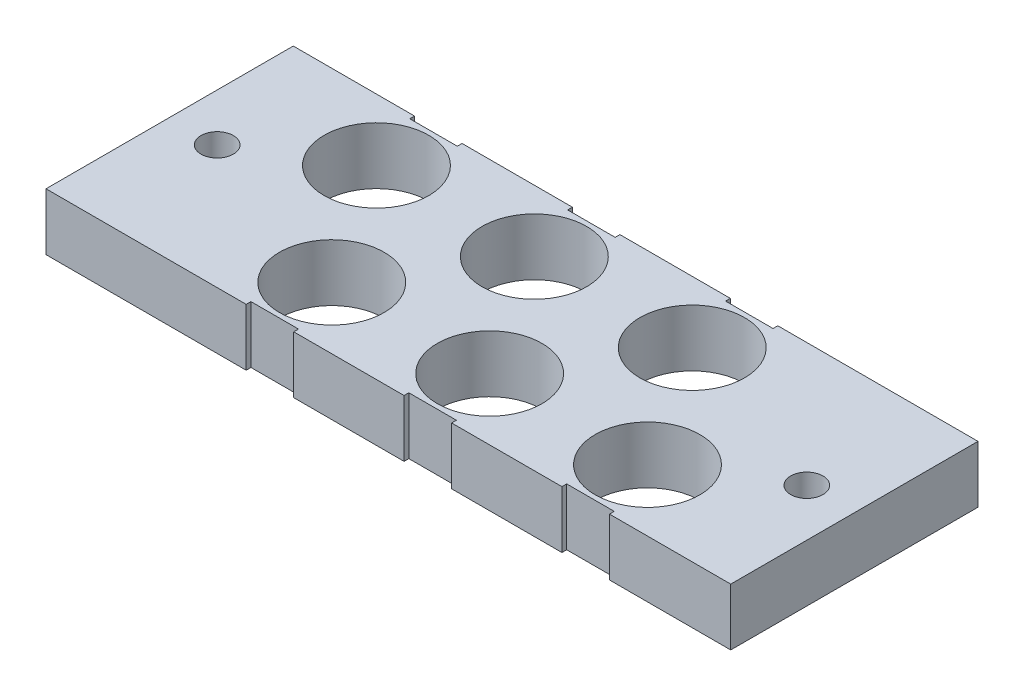
SolidWorks part; units mm, degrees
ref_plane "Front Plane" through (0, 0, 0) normal (0, 0, 1) x (1, 0, 0)
ref_plane "Top Plane" through (0, 0, 0) normal (0, 1, 0) x (1, 0, 0)
ref_plane "Right Plane" through (0, 0, 0) normal (1, 0, 0) x (0, 0, -1)
sketch "Sketch1" plane through (0, 0, 0) normal (0, 1, 0) x (1, 0, 0)
  line L0 (5.3864, -4.1649) -> (1.7864, -4.1649)
  line L1 (18.3864, -4.1649) -> (21.9864, -4.1649)
  line L2 (30.2864, -30.1649) -> (26.6864, -30.1649)
  line L3 (13.6864, -30.1649) -> (10.0864, -30.1649)
  line L4 (43.2864, -30.1649) -> (52.0364, -30.1649)
  line L5 (52.0364, -30.1649) -> (52.0364, -4.1649)
  line L6 (52.0364, -4.1649) -> (34.9864, -4.1649)
  line L7 (-11.2136, -4.1649) -> (-19.9636, -4.1649)
  line L8 (-19.9636, -4.1649) -> (-19.9636, -30.1649)
  line L9 (-19.9636, -30.1649) -> (-2.9136, -30.1649)
  line L10 (-14.9636, -4.1649) -> (-14.9636, -30.1649) construction
  line L11 (47.0364, -4.1649) -> (47.0364, -30.1649) construction
  circle A0 centre (-14.9636, -17.1649) radius 1.7
  circle A1 centre (47.0364, -17.1649) radius 1.7
  line B0 (34.9864, -17.1649) -> (34.9864, -4.1649)
  line B1 (10.0864, -30.1649) -> (6.0864, -30.1649)
  line B2 (-2.4136, -29.6649) -> (9.5864, -29.6649)
  line B3 (10.0864, -30.1649) -> (10.0864, -17.1649)
  line B4 (26.6864, -30.1649) -> (26.6864, -17.1649)
  line B5 (43.2864, -30.1649) -> (43.2864, -17.1649)
  line B6 (-2.9136, -17.1649) -> (-2.9136, -30.1649)
  line B7 (9.5864, -29.6649) -> (9.5864, -17.6649)
  line B8 (30.2864, -17.1649) -> (30.2864, -30.1649)
  line B9 (21.9864, -4.1649) -> (21.9864, -17.1649)
  line B10 (34.4864, -16.6649) -> (34.4864, -4.6649)
  line B11 (17.8864, -16.6649) -> (17.8864, -4.6649)
  line B12 (1.7864, -17.1649) -> (1.7864, -4.1649)
  line B13 (42.7864, -29.6649) -> (42.7864, -17.6649)
  line B14 (14.1864, -29.6649) -> (26.1864, -29.6649)
  line B15 (30.7864, -17.6649) -> (30.7864, -29.6649)
  line B16 (30.7864, -17.6649) -> (42.7864, -29.6649) construction
  line B17 (14.1864, -17.6649) -> (26.1864, -29.6649) construction
  line B18 (-2.4136, -17.6649) -> (9.5864, -29.6649) construction
  line B19 (43.2864, -17.1649) -> (30.2864, -17.1649)
  line B20 (1.2864, -16.6649) -> (1.2864, -4.6649)
  line B21 (14.1864, -17.6649) -> (14.1864, -29.6649)
  line B22 (26.6864, -30.1649) -> (22.6864, -30.1649)
  line B23 (30.2864, -30.1649) -> (34.2864, -30.1649)
  line B24 (43.2864, -30.1649) -> (39.2864, -30.1649)
  line B25 (-10.7136, -10.6649) -> (1.2864, -10.6649) construction
  line B26 (5.8864, -10.6649) -> (17.8864, -10.6649) construction
  line B27 (22.4864, -10.6649) -> (34.4864, -10.6649) construction
  line B28 (-2.4136, -23.6649) -> (9.5864, -23.6649) construction
  line B29 (14.1864, -23.6649) -> (26.1864, -23.6649) construction
  line B30 (30.7864, -23.6649) -> (42.7864, -23.6649) construction
  line B31 (-27.9152, -23.6649) -> (50.7342, -23.6649) construction
  line B32 (21.9864, -17.1649) -> (34.9864, -17.1649)
  line B33 (-27.9152, -10.6649) -> (50.7342, -10.6649) construction
  line B34 (28.4864, -16.6649) -> (28.4864, -4.6649) construction
  line B35 (36.7864, -17.6649) -> (36.7864, -29.6649) construction
  line B36 (20.1864, -17.6649) -> (20.1864, -29.6649) construction
  line B37 (11.8864, -16.6649) -> (11.8864, -4.6649) construction
  line B38 (3.5864, -17.6649) -> (3.5864, -29.6649) construction
  line B39 (-4.7136, -16.6649) -> (-4.7136, -4.6649) construction
  line B40 (22.4864, -4.6649) -> (22.4864, -16.6649)
  line B41 (22.4864, -16.6649) -> (34.4864, -16.6649)
  line B42 (34.4864, -4.6649) -> (22.4864, -4.6649)
  line B43 (34.4864, -16.6649) -> (22.4864, -4.6649) construction
  line B44 (34.4864, -4.6649) -> (22.4864, -16.6649) construction
  line B45 (34.9864, -4.1649) -> (30.9864, -4.1649)
  line B46 (21.9864, -4.1649) -> (25.9864, -4.1649)
  line B47 (30.9864, -4.1649) -> (30.9864, -4.6649)
  line B48 (25.9864, -4.1649) -> (25.9864, -4.6649)
  circle B49 centre (28.4864, -10.6649) radius 5.5
  line B50 (-2.4136, -17.6649) -> (-2.4136, -29.6649)
  line B51 (9.5864, -17.6649) -> (-2.4136, -17.6649)
  line B52 (-2.4136, -29.6649) -> (9.5864, -17.6649) construction
  line B53 (10.0864, -17.1649) -> (-2.9136, -17.1649)
  line B54 (-2.9136, -30.1649) -> (1.0864, -30.1649)
  line B55 (1.0864, -30.1649) -> (1.0864, -29.6649)
  line B56 (6.0864, -30.1649) -> (6.0864, -29.6649)
  circle B57 centre (3.5864, -23.6649) radius 5.5
  line B58 (26.1864, -29.6649) -> (26.1864, -17.6649)
  line B59 (26.1864, -17.6649) -> (14.1864, -17.6649)
  line B60 (14.1864, -29.6649) -> (26.1864, -17.6649) construction
  line B61 (26.6864, -17.1649) -> (13.6864, -17.1649)
  line B62 (13.6864, -17.1649) -> (13.6864, -30.1649)
  line B63 (13.6864, -30.1649) -> (17.6864, -30.1649)
  line B64 (17.6864, -30.1649) -> (17.6864, -29.6649)
  line B65 (22.6864, -30.1649) -> (22.6864, -29.6649)
  circle B66 centre (20.1864, -23.6649) radius 5.5
  line B67 (42.7864, -17.6649) -> (30.7864, -17.6649)
  line B68 (30.7864, -29.6649) -> (42.7864, -29.6649)
  line B69 (30.7864, -29.6649) -> (42.7864, -17.6649) construction
  line B70 (34.2864, -30.1649) -> (34.2864, -29.6649)
  line B71 (39.2864, -30.1649) -> (39.2864, -29.6649)
  circle B72 centre (36.7864, -23.6649) radius 5.5
  line B73 (5.8864, -4.6649) -> (5.8864, -16.6649)
  line B74 (5.8864, -16.6649) -> (17.8864, -16.6649)
  line B75 (17.8864, -4.6649) -> (5.8864, -4.6649)
  line B76 (17.8864, -16.6649) -> (5.8864, -4.6649) construction
  line B77 (17.8864, -4.6649) -> (5.8864, -16.6649) construction
  line B78 (5.3864, -17.1649) -> (18.3864, -17.1649)
  line B79 (18.3864, -17.1649) -> (18.3864, -4.1649)
  line B80 (5.3864, -4.1649) -> (5.3864, -17.1649)
  line B81 (18.3864, -4.1649) -> (14.3864, -4.1649)
  line B82 (5.3864, -4.1649) -> (9.3864, -4.1649)
  line B83 (14.3864, -4.1649) -> (14.3864, -4.6649)
  line B84 (9.3864, -4.1649) -> (9.3864, -4.6649)
  circle B85 centre (11.8864, -10.6649) radius 5.5
  line B86 (-10.7136, -4.6649) -> (-10.7136, -16.6649)
  line B87 (-10.7136, -16.6649) -> (1.2864, -16.6649)
  line B88 (1.2864, -4.6649) -> (-10.7136, -4.6649)
  line B89 (1.2864, -16.6649) -> (-10.7136, -4.6649) construction
  line B90 (1.2864, -4.6649) -> (-10.7136, -16.6649) construction
  line B91 (-11.2136, -17.1649) -> (1.7864, -17.1649)
  line B92 (-11.2136, -4.1649) -> (-11.2136, -17.1649)
  line B93 (1.7864, -4.1649) -> (-2.2136, -4.1649)
  line B94 (-11.2136, -4.1649) -> (-7.2136, -4.1649)
  line B95 (-2.2136, -4.1649) -> (-2.2136, -4.6649)
  line B96 (-7.2136, -4.1649) -> (-7.2136, -4.6649)
  circle B97 centre (-4.7136, -10.6649) radius 5.5
  dimension "D1" = 8.75
  dimension "D2" = 8.75
  dimension "D3" = 5
  dimension "D4" = 5
sketch_block_instance "Block1-5"
sketch_block "Block1" parameters "D3"=6, "D1"=12, "D2"=12, "D4"=12, "D5"=78.6494, "D6"=78.6494, "D7"=78.6494, "D8"=10.3235, "D9"=14.0261, "D10"=17.7654, "D11"=23.7534, "D12"=22.7743, "D13"=54.5
sketch_block_instance "Block2-2"
sketch_block "Block2" parameters "D2"=8, "D1"=12
sketch_block_instance "Block2-3"
sketch_block_instance "Block2-4"
sketch_block_instance "Block2-5"
sketch_block_instance "Block2-6"
sketch_block_instance "Block2-7"
sketch_block_instance "Block3-1"
sketch_block "Block3"
sketch_block_instance "Block4-1"
sketch_block "Block4"
sketch_block_instance "Block5-1"
sketch_block "Block5"
sketch_block_instance "Block6-1"
sketch_block "Block6"
sketch_block_instance "Block7-1"
sketch_block "Block7"
sketch_block_instance "Block8-1"
sketch_block "Block8"
extrude "Boss-Extrude1" add sketch "Sketch1" against normal blind 6 contours B50 B2 B7 B51 B57 | B20 B88 B86 B87 B97 | B11 B75 B73 B74 B85 | B21 B14 B58 B59 B66 | B10 B42 B40 B41 B49 | B15 B68 B13 B67 B72 region at (11.8864, 0, 4.8346) region at (-0.4636, 0, 4.8346) region at (3.5864, 0, 29.4952) region at (15.9364, 0, 29.4952) region at (28.4864, 0, 4.8346) region at (32.5364, 0, 29.4952)
extrude "Boss-Extrude2" add sketch "Sketch1<3>" against normal blind 6 contours B92 L7 L8 L9 B6 B91 A0 | B5 L4 L5 L6 B0 B19 A1 | B78 B3 L3 B62 | B8 B32 B4 L2 | B12 B53 B80 L0 | B79 B61 B9 L1 | B56 B1 B3 B53 B6 B54 B55 B2 B50 B51 B7 | B65 B22 B4 B32 B61 B62 B63 B64 B14 B21 B59 B58 | B71 B24 B5 B19 B32 B8 B23 B70 B68 B15 B67 B13 | B48 B46 B9 B32 B0 B45 B47 B42 B10 B41 B40 | B84 B82 B80 B53 B78 B61 B79 B81 B83 B75 B11 B74 B73 | B96 B94 B92 B91 B53 B12 B93 B95 B88 B20 B87 B86 region at (3.5864, 0, 10.6649) region at (7.3864, 0, 4.3487) region at (1.6025, 0, 10.6649) region at (7.7364, 0, 17.3487) region at (11.8864, 0, 23.6649) region at (-12.7872, 0, 19.3141) region at (16.0364, 0, 17.3487) region at (20.1864, 0, 10.6649) region at (22.1702, 0, 10.6649) region at (28.4864, 0, 23.6649) region at (32.6364, 0, 17.3487) region at (44.8599, 0, 15.0156)
sketch "Sketch1<3>" plane through (0, 0, 0) normal (0, 1, 0) x (1, 0, 0) same geometry as "Sketch1"
sketch "Sketch2" plane through (0, -6, 0) normal (0, -1, 0) x (-1, 0, 0)
  text T0 "F8"
extrude "Cut-Extrude1" cut sketch "Sketch2" against normal blind 1
